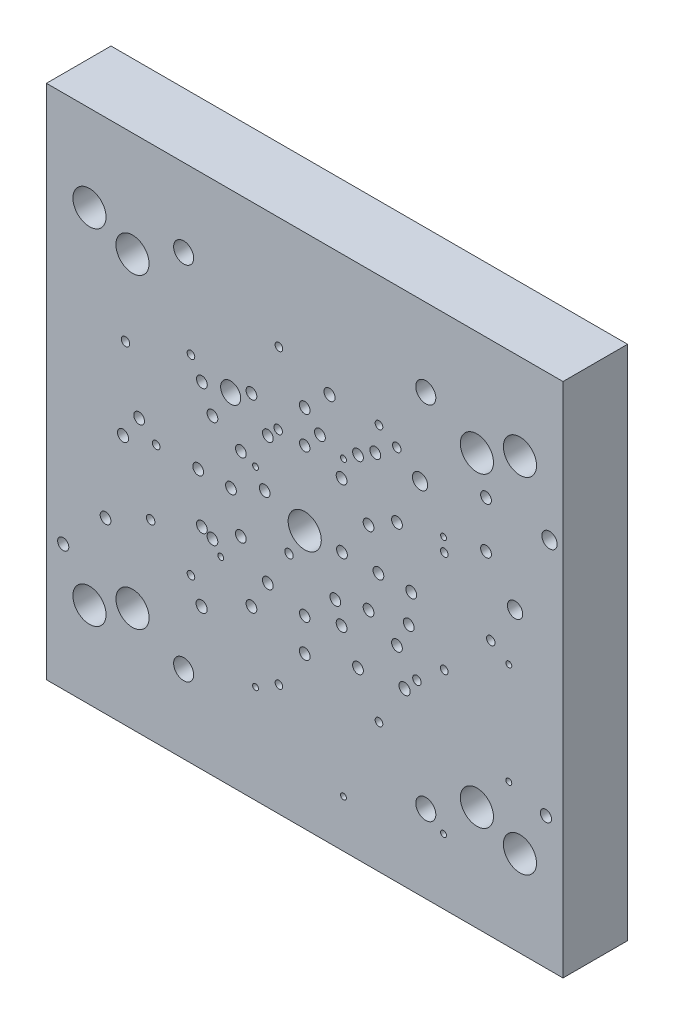
SolidWorks part; units mm, degrees
ref_plane "Front Plane" through (0, 0, 0) normal (0, 0, 1) x (1, 0, 0)
ref_plane "Top Plane" through (0, 0, 0) normal (0, 1, 0) x (1, 0, 0)
ref_plane "Right Plane" through (0, 0, 0) normal (1, 0, 0) x (0, 0, -1)
sketch "Sketch1" plane through (0, 0, 0) normal (0, 0, 1) x (1, 0, 0)
  line L1 (-152.4, 152.4) -> (152.4, 152.4)
  line L2 (-152.4, 152.4) -> (-152.4, -152.4)
  line L3 (-152.4, -152.4) -> (152.4, -152.4)
  line L4 (152.4, 152.4) -> (152.4, -152.4)
  line L5 (-152.4, 152.4) -> (152.4, -152.4) construction
  line L6 (-152.4, -152.4) -> (152.4, 152.4) construction
  point P0 (0, 0)
  dimension "D1" = 304.8
  dimension "D2" = 304.8
extrude "Boss-Extrude1" add sketch "Sketch1" along normal blind 38.1
sketch "Sketch2" plane through (0, 0, 38.1) normal (0, 0, 1) x (1, 0, 0)
  line L0 (-152.4, 0) -> (152.4, 0) construction
  line L5 (-152.4, 152.4) -> (-152.4, -152.4) construction
  line L6 (152.4, -152.4) -> (152.4, 152.4) construction
  line L7 (-152.4, -101.6) -> (152.4, -101.6) construction
  line L8 (-152.4, 101.6) -> (152.4, 101.6) construction
  line L9 (0, 101.6) -> (0, -101.6) construction
  line L10 (127, 101.6) -> (127, -101.6) construction
  line L11 (-127, 101.6) -> (-127, -101.6) construction
  circle A0 centre (-127, 101.6) radius 6.5151
  circle A1 centre (127, 101.6) radius 6.5151
  circle A2 centre (127, -101.6) radius 6.5151
  circle A3 centre (-127, -101.6) radius 6.5151
  circle A4 centre (0, 0) radius 6.5151
  dimension "D5" = 13.0302
  dimension "D1" = 101.6
  dimension "D2" = 101.6
  dimension "D3" = 127
  dimension "D4" = 127
extrude "HAAS T-Slot Holes" cut sketch "Sketch2" against normal through all
sketch "Sketch3" plane through (0, 0, 38.1) normal (0, 0, 1) x (1, 0, 0)
  circle A0 centre (-127, 101.6) radius 9.779
  circle A1 centre (127, 101.6) radius 9.779
  circle A2 centre (0, 0) radius 9.779
  circle A3 centre (127, -101.6) radius 9.779
  circle A4 centre (-127, -101.6) radius 9.779
  dimension "D1" = 19.558
extrude "HAAS Counter Bores" cut sketch "Sketch3" against normal offset from surface (22.225 mm away) 15.875 contours A0 | A1 | A2 | A3 | A4 up to face at (6.5151, 0, 0)
sketch "Sketch4" plane through (0, 0, 38.1) normal (0, 0, 1) x (1, 0, 0)
  line L0 (-127, 90.4875) -> (127, 90.4875) construction
  line L1 (-127, 30.1625) -> (127, 30.1625) construction
  line L2 (-127, 30.1625) -> (-127, -30.1625) construction
  line L3 (-127, -30.1625) -> (127, -30.1625) construction
  line L4 (127, 30.1625) -> (127, -30.1625) construction
  line L5 (-127, 30.1625) -> (127, -30.1625) construction
  line L6 (-127, -30.1625) -> (127, 30.1625) construction
  line L7 (-127, -90.4875) -> (127, -90.4875) construction
  line L8 (-101.6, 90.4875) -> (-101.6, 84.1375) construction
  line L9 (-101.6, -90.4875) -> (-101.6, -84.1375) construction
  line L10 (101.6, -90.4875) -> (101.6, -84.1375) construction
  line L11 (101.6, 90.4875) -> (101.6, 84.1375) construction
  circle A0 centre (-101.6, 90.4875) radius 6.5151
  circle A1 centre (101.6, 90.4875) radius 6.5151
  circle A2 centre (-101.6, -90.4875) radius 6.5151
  circle A3 centre (101.6, -90.4875) radius 6.5151
  point P0 (0, 0)
  dimension "D9" = 13.0302
  dimension "D1" = 60.325
  dimension "D2" = 254
  dimension "D5" = 203.2
  dimension "D6" = 25.4
  dimension "D7" = 203.2
  dimension "D8" = 6.35
  dimension "D3" = 60.325
  dimension "D4" = 60.325
extrude "Tormach T-Slot Holes" cut sketch "Sketch4" against normal through all
sketch "Sketch5" plane through (0, 0, 38.1) normal (0, 0, 1) x (1, 0, 0)
  circle A0 centre (-101.6, 90.4875) radius 9.779
  circle A1 centre (101.6, 90.4875) radius 9.779
  circle A2 centre (101.6, -90.4875) radius 9.779
  circle A3 centre (-101.6, -90.4875) radius 9.779
  dimension "D1" = 19.558
extrude "Tormach Counter bores" cut sketch "Sketch5" against normal up to surface (22.225 mm away) up to face at (-117.221, 101.6, 15.875)
sketch "Sketch6" plane through (0, 0, 38.1) normal (0, 0, 1) x (1, 0, 0)
  circle A0 centre (0, 0) radius 43.5 construction
  circle A1 centre (0, 43.5) radius 3.0734
  circle A2 centre (0, -43.5) radius 3.0734
  dimension "D1" = 87.0001
  dimension "D2" = 6.1468
extrude "Sprocket Locating Holes" cut sketch "Sketch6" against normal blind 6.35
sketch "Sketch7" plane through (0, 0, 38.1) normal (0, 0, 1) x (1, 0, 0)
  circle A0 centre (0, 0) radius 43.5 construction
  circle A2 centre (43.5, 0) radius 3.175
  circle A4 centre (37.6721, -21.75) radius 3.175
  circle A5 centre (21.75, -37.6721) radius 3.175
  circle A6 centre (0, -43.5) radius 3.175 [skipped]
  circle A7 centre (-21.75, -37.6721) radius 3.175
  circle A8 centre (-37.6721, -21.75) radius 3.175
  circle A9 centre (-43.5, 0) radius 3.175
  circle A10 centre (-37.6721, 21.75) radius 3.175
  circle A11 centre (-21.75, 37.6721) radius 3.175
  circle A12 centre (0, 43.5) radius 3.175 [skipped]
  circle A13 centre (21.75, 37.6721) radius 3.175
  circle A14 centre (37.6721, 21.75) radius 3.175
  point P31 (0, 0)
  dimension "D1" = 87.0001
  dimension "D2" = 6.35
  dimension "D3" = 12
extrude "Sprocket Mounting clearance holes" cut sketch "Sketch7" against normal blind 9.525
sketch "Sketch8" plane through (0, 0, 38.1) normal (0, 0, 1) x (1, 0, 0)
  line L1 (-71.4375, 106.4641) -> (71.4375, 106.4641) construction
  line L2 (-71.4375, 106.4641) -> (-71.4375, -106.4641) construction
  line L3 (-71.4375, -106.4641) -> (71.4375, -106.4641) construction
  line L4 (71.4375, 106.4641) -> (71.4375, -106.4641) construction
  line L5 (-71.4375, 106.4641) -> (71.4375, -106.4641) construction
  line L6 (-71.4375, -106.4641) -> (71.4375, 106.4641) construction
  circle A0 centre (-71.4375, 106.4641) radius 5.9182
  circle A1 centre (71.4375, 106.4641) radius 5.9182
  circle A2 centre (71.4375, -106.4641) radius 5.9182
  circle A3 centre (-71.4375, -106.4641) radius 5.9182
  point P0 (0, 0)
  dimension "D3" = 11.8364
  dimension "D1" = 142.875
  dimension "D2" = 212.9282
extrude "1/2-13 Tapped Holes" cut sketch "Sketch8" against normal blind 19.05
sketch "Sketch9" plane through (0, 0, 38.1) normal (0, 0, 1) x (1, 0, 0)
  circle A0 centre (-117.5189, -52.2876) radius 3.175
  circle A1 centre (-60.6634, -28.4101) radius 3.175
  circle A2 centre (-60.6634, 45.677) radius 3.175
  circle A3 centre (-23.6198, 8.6335) radius 3.175
  circle A4 centre (-97.707, 8.6335) radius 3.175
  circle A5 centre (18.0623, -26.1797) radius 3.175
  circle A6 centre (21.9762, 0) radius 3.175
  circle A7 centre (61.3833, -17.3739) radius 3.175
  circle A8 centre (106.976, 70.3959) radius 3.175
  circle A9 centre (106.976, 42.9004) radius 3.175
  circle A10 centre (144.4539, 67.4373) radius 4.5
  circle A11 centre (124.1092, 21.6131) radius 4.5
  circle A12 centre (68.0681, 59.3279) radius 4.5
  circle A13 centre (58.9353, -51.2652) radius 3.3
  circle A14 centre (-142.4923, -78.095) radius 3.3
  circle A15 centre (-105.7351, 43.7713) radius 2.5
  circle A16 centre (-90.8975, -39.8642) radius 2.5
  circle A17 centre (-9.2711, -16.3656) radius 2.5
  circle A18 centre (-15.6655, 43.8657) radius 2.5
  circle A20 centre (14.6267, 76.8405) radius 3.3
  circle A21 centre (8.9855, 53.4682) radius 3.175
  circle A22 centre (41.6559, 60.6579) radius 3.175
extrude "SSB Holes" cut sketch "Sketch9" against normal blind 19.05
ref_axis "Axis1" through (0, 0, 0) along (0, 0, 1)
sketch "Sketch10" plane through (0, 0, 38.1) normal (0, 0, 1) x (1, 0, 0)
  circle A0 centre (0, 0) radius 62.865 construction
  circle A1 centre (0, 62.865) radius 3.175
  circle A13 centre (31.4325, 54.4427) radius 3.175
  circle A14 centre (54.4427, 31.4325) radius 3.175
  circle A15 centre (62.865, 0) radius 3.175
  circle A16 centre (54.4427, -31.4325) radius 3.175
  circle A17 centre (31.4325, -54.4427) radius 3.175
  circle A18 centre (0, -62.865) radius 3.175
  circle A19 centre (-31.4325, -54.4427) radius 3.175
  circle A20 centre (-54.4427, -31.4325) radius 3.175
  circle A21 centre (-62.865, 0) radius 3.175
  circle A22 centre (-54.4427, 31.4325) radius 3.175
  circle A23 centre (-31.4325, 54.4427) radius 3.175
  point P30 (0, 0)
  point P56 (0, 0)
  dimension "D1" = 125.73
  dimension "D2" = 6.35
  dimension "D4" = 12
extrude "Sprocket Countersunk Holes" cut sketch "Sketch10" against normal blind 19.05
sketch "Sketch12" plane through (0, 0, 38.1) normal (0, 0, 1) x (1, 0, 0)
  circle A0 centre (-107.2144, -4.9977) radius 3.3
  circle A1 centre (-60.8212, -69.1392) radius 3.3
  circle A2 centre (142.3129, -74.567) radius 3.3
  circle A4 centre (54.3307, 69.7186) radius 2.4964
  circle A5 centre (109.7823, -1.2607) radius 2.5
  circle A6 centre (66.2094, -43.3332) radius 2.5
  circle A7 centre (-43.6886, 48.7489) radius 5.9182
  circle A8 centre (-71.4375, 106.4641) radius 5.9182 construction
extrude "DSB Holes" cut sketch "Sketch12" against normal blind 19.05
sketch "Brake Rotor Toe Clamp Holes" plane through (0, 0, 38.1) normal (0, 0, 1) x (1, 0, 0)
  line L0 (-74.6653, 106.6331) -> (74.6653, -106.6331) construction
  line L1 (74.6653, 106.6331) -> (-74.6653, -106.6331) construction
  line L6 (0, 0) -> (192.0367, 0) construction
  line L7 (0, 0) -> (-160.9096, 0) construction
  line L8 (0, 0) -> (0, 219.8313) construction
  line L9 (0, 0) -> (-215.8918, 38.0675) construction
  circle A0 centre (0, 0) radius 130.175 construction
  circle A10 centre (-87.63, 0) radius 2.3813 construction
  circle A12 centre (-74.93, 0) radius 2.3813 construction
  circle A13 centre (-80.0452, 14.1141) radius 2.3813
  circle A14 centre (-70.4112, 25.6276) radius 2.3812 construction
  circle A15 centre (-70.3905, 40.64) radius 2.3812 construction
  circle A16 centre (-82.3453, 29.9712) radius 2.3812 construction
  circle A17 centre (-57.3997, 48.1641) radius 2.3813 construction
  circle A18 centre (-52.2458, 62.2641) radius 2.3812
  circle A19 centre (-67.1285, 56.3275) radius 2.3812 construction
  circle A20 centre (-37.465, 64.8913) radius 2.3813 construction
  circle A21 centre (-27.7994, 76.3782) radius 2.3813 construction
  circle A22 centre (-43.815, 75.8898) radius 2.3813 construction
  circle A23 centre (-13.0115, 73.7916) radius 2.3813 construction
  circle A24 centre (0, 81.28) radius 2.3813
  circle A25 centre (-15.2168, 86.2987) radius 2.3813 construction
  circle A26 centre (13.0115, 73.7916) radius 2.3812 construction
  circle A27 centre (27.7994, 76.3782) radius 2.3812 construction
  circle A28 centre (15.2168, 86.2987) radius 2.3813 construction
  circle A29 centre (37.465, 64.8913) radius 2.3812 construction
  circle A30 centre (52.2458, 62.2641) radius 2.3813
  circle A31 centre (43.815, 75.8898) radius 2.3812 construction
  circle A32 centre (57.3997, 48.1641) radius 2.3813 construction
  circle A33 centre (70.3905, 40.64) radius 2.3813 construction
  circle A34 centre (67.1285, 56.3275) radius 2.3813 construction
  circle A35 centre (70.4112, 25.6276) radius 2.3813 construction
  circle A36 centre (80.0452, 14.1141) radius 2.3813
  circle A37 centre (82.3453, 29.9712) radius 2.3813 construction
  circle A38 centre (74.93, 0) radius 2.3813 construction
  circle A39 centre (80.0452, -14.1141) radius 2.3813 construction
  circle A40 centre (87.63, 0) radius 2.3813 construction
  circle A41 centre (70.4112, -25.6276) radius 2.3812 construction
  circle A42 centre (70.3905, -40.64) radius 2.3813
  circle A43 centre (82.3453, -29.9712) radius 2.3812 construction
  circle A44 centre (57.3997, -48.1641) radius 2.3813 construction
  circle A45 centre (52.2458, -62.2641) radius 2.3813 construction
  circle A46 centre (67.1285, -56.3275) radius 2.3812 construction
  circle A47 centre (37.465, -64.8913) radius 2.3813 construction
  circle A48 centre (27.7994, -76.3782) radius 2.3813
  circle A49 centre (43.815, -75.8898) radius 2.3813 construction
  circle A50 centre (13.0115, -73.7916) radius 2.3813 construction
  circle A51 centre (0, -81.28) radius 2.3812 construction
  circle A52 centre (15.2168, -86.2987) radius 2.3813 construction
  circle A53 centre (-13.0115, -73.7916) radius 2.3813 construction
  circle A54 centre (-27.7994, -76.3782) radius 2.3813
  circle A55 centre (-15.2168, -86.2987) radius 2.3813 construction
  circle A56 centre (-37.465, -64.8913) radius 2.3813 construction
  circle A57 centre (-52.2458, -62.2641) radius 2.3813 construction
  circle A58 centre (-43.815, -75.8898) radius 2.3812 construction
  circle A59 centre (-57.3997, -48.1641) radius 2.3813 construction
  circle A60 centre (-70.3905, -40.64) radius 2.3813
  circle A61 centre (-67.1285, -56.3275) radius 2.3813 construction
  circle A62 centre (-70.4112, -25.6276) radius 2.3813 construction
  circle A63 centre (-80.0452, -14.1141) radius 2.3813 construction
  circle A64 centre (-82.3453, -29.9712) radius 2.3813 construction
  point P27 (0, 0)
  point P130 (0, 0)
  dimension "D1" = 260.35
  dimension "D17" = 4.7625
  dimension "D18" = 81.28
  dimension "D19" = 18
  dimension "D14" = 4.7625
  dimension "D15" = 4.7625
  dimension "D10" = 55
  dimension "D11" = 55
  dimension "D12" = 87.63
  dimension "D13" = 12.7
  dimension "D16" = 10
hole_wizard "Rotor Clamp Bolts" positions "Sketch15" profile "Sketch16" hole size "M4" standard "AS"
sketch "Sketch15" plane through (0, 0, 38.1) normal (0, 0, 1) x (1, 0, 0)
  point P0 (-87.63, 0)
  point P3 (-67.1285, -56.3275)
  point P6 (-15.2168, -86.2987)
  point P9 (43.815, -75.8898)
  point P12 (82.3453, -29.9712)
  point P15 (82.3453, 29.9712)
  point P18 (43.815, 75.8898)
  point P21 (-15.2168, 86.2987)
  point P24 (-67.1285, 56.3275)
sketch "Sketch16" plane through (-87.63, 0, 38.1) normal (1, 0, 0) x (0, -1, 0)
  line L0 (0, 0) -> (0, 20.4019)
  line L1 (0, 20.4019) -> (2.25, 19.05)
  line L2 (2.25, 19.05) -> (2.25, 0)
  line L5 (2.25, 0) -> (0, 0)
  line L10 (0, 20.4019) -> (-2.25, 19.05) construction
  line L11 (0, -6.35) -> (0, 107.95) construction
  dimension "Hole Dia." = 4.5
  dimension "Hole Depth" = 19.05
  dimension "Drill Angle" = 118
sketch "Sketch17" plane through (0, 0, 38.1) normal (0, 0, 1) x (1, 0, 0)
  line L0 (-152.4, -152.4) -> (152.4, -152.4) construction
  line L1 (152.4, 152.4) -> (-21.7714, 152.4)
  line L2 (152.4, 152.4) -> (152.4, -152.4)
  line L3 (152.4, -152.4) -> (-75.5158, -152.4)
  line L5 (-21.7714, 152.4) -> (-75.5158, -152.4)
  point P7 (-73.5632, -152.4)
  dimension "D1" = 80
sketch "New Rotor Holes" plane through (0, 0, 38.1) normal (0, 0, 1) x (1, 0, 0)
  circle A0 centre (38.1, -38.1) radius 87.63 construction
  circle A1 centre (-49.53, -38.1) radius 1.7272
  circle A2 centre (-29.0285, -94.4275) radius 1.7272
  circle A3 centre (22.8832, -124.3987) radius 1.7272
  circle A4 centre (81.915, -113.9898) radius 1.7272
  circle A5 centre (120.4453, -68.0712) radius 1.7272
  circle A6 centre (120.4453, -8.1288) radius 1.7272
  circle A7 centre (81.915, 37.7898) radius 1.7272
  circle A8 centre (22.8832, 48.1987) radius 1.7272
  circle A9 centre (-29.0285, 18.2275) radius 1.7272
  point P5 (25.4, -25.4)
  point P24 (38.1, -38.1)
  dimension "D3" = 175.26
  dimension "D4" = 3.4544
  dimension "D1" = 38.1
  dimension "D2" = 38.1
  dimension "D5" = 9
extrude "12-28 RotorHoles " cut sketch "New Rotor Holes" against normal blind 19.05
equation "\"boltRotor\"=0.75"
equation "\"bolt\"=0.51159"
